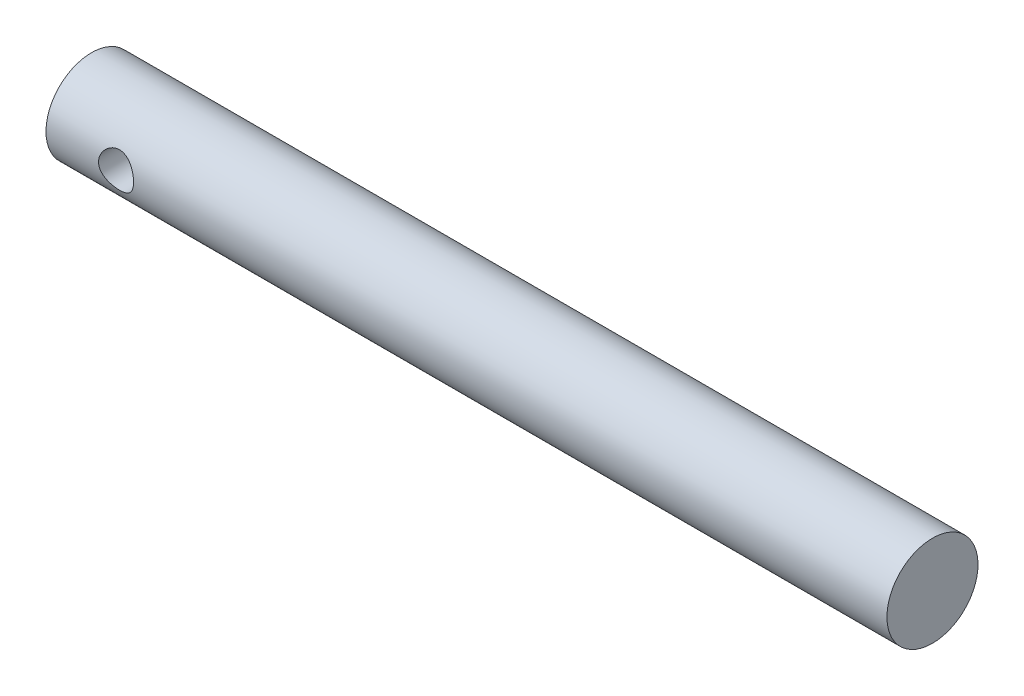
SolidWorks part; units mm, degrees
material "ABS"
ref_plane "Front Plane" through (0, 0, 0) normal (0, 0, 1) x (1, 0, 0)
ref_plane "Top Plane" through (0, 0, 0) normal (0, 1, 0) x (1, 0, 0)
ref_plane "Right Plane" through (0, 0, 0) normal (1, 0, 0) x (0, 0, -1)
sketch "Sketch2" plane through (0, 0, 0) normal (0, 0, 1) x (1, 0, 0)
  line L0 (0, 0) -> (0, -1.95) construction
  line L5 (-18, 0) -> (18, 0)
  line L6 (-18, 0) -> (-18, -1.95)
  line L7 (-18, -1.95) -> (18, -1.95)
  line L8 (18, 0) -> (18, -1.95)
  line L9 (-15, 0) -> (-15, 0.75) construction
  circle A0 centre (-15, 0) radius 0.75
  point P8 (0, 0)
  dimension "D1" = 36
  dimension "D2" = 1.95
  dimension "D3" = 0.75
  dimension "D4" = 3
revolve "Revolve2" add sketch "Sketch2" angle 360 about L5 region at (0.1912, -0.9834, 0)
extrude "Cut-Extrude1" cut sketch "Sketch2<3>" against normal through all both and the other way through all contours A0
sketch "Sketch2<3>" plane through (0, 0, 0) normal (0, 0, 1) x (1, 0, 0) same geometry as "Sketch2"
